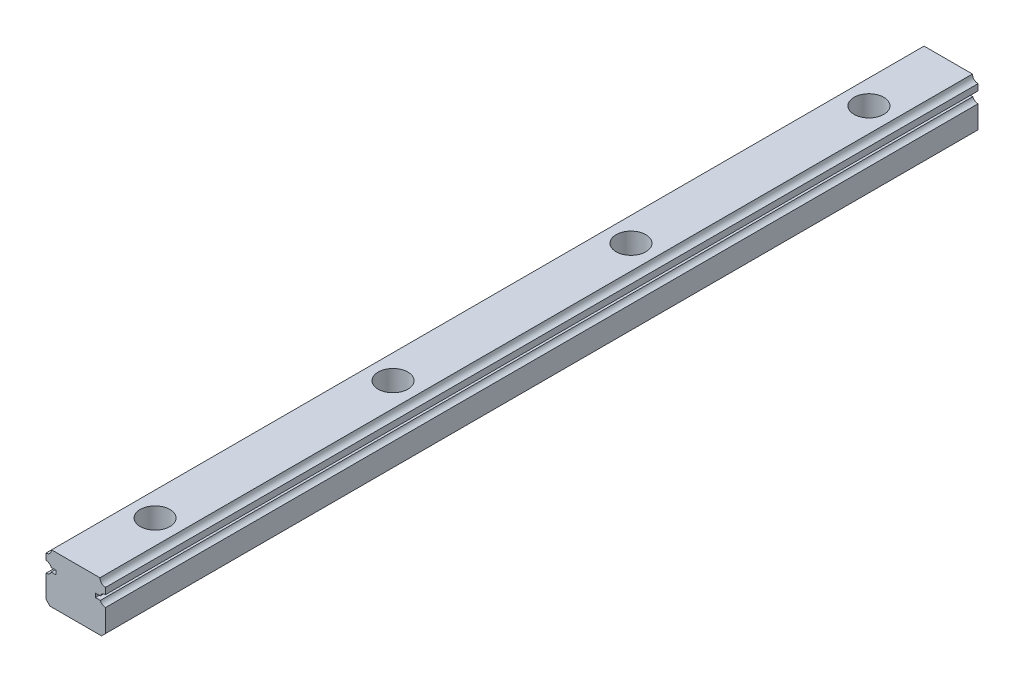
SolidWorks part; units mm, degrees
ref_plane "Front" through (0, 0, 0) normal (0, 0, 1) x (1, 0, 0)
ref_plane "Top" through (0, 0, 0) normal (0, 1, 0) x (1, 0, 0)
ref_plane "Right" through (0, 0, 0) normal (1, 0, 0) x (0, 0, -1)
sketch "15mm" plane through (0, 0, 0) normal (0, 0, 1) x (1, 0, 0)
  line L0 (0, 0) -> (0, 12.5) construction
  line L2 (4.95, 7.6) -> (6.1923, 7.6)
  line L3 (4.95, 8.6) -> (4.95, 7.6)
  line L4 (6.1923, 8.6) -> (4.95, 8.6)
  line L5 (7.5, 11.1) -> (7.5, 9.5)
  line L6 (-6.1, 12.5) -> (6.1, 12.5)
  line L7 (-7.5, 9.5) -> (-7.5, 11.1)
  line L8 (-4.95, 8.6) -> (-6.1923, 8.6)
  line L9 (-4.95, 7.6) -> (-4.95, 8.6)
  line L10 (-6.1923, 7.6) -> (-4.95, 7.6)
  line L11 (-7.5, 1) -> (-7.5, 6.7)
  line L12 (-6.5, 0) -> (-7.5, 1)
  line L13 (6.5, 0) -> (-6.5, 0)
  line L14 (7.5, 1) -> (6.5, 0)
  line L15 (7.5, 6.7) -> (7.5, 1)
  arc A0 (6.1923, 8.6) -> (7.5, 9.5) centre (7.5, 8.1) cw
  arc A1 (7.5, 11.1) -> (6.1, 12.5) centre (7.5, 12.5) cw
  arc A2 (-6.1, 12.5) -> (-7.5, 11.1) centre (-7.5, 12.5) cw
  arc A3 (-7.5, 9.5) -> (-6.1923, 8.6) centre (-7.5, 8.1) cw
  arc A4 (-6.1923, 7.6) -> (-7.5, 6.7) centre (-7.5, 8.1) cw
  arc A5 (7.5, 6.7) -> (6.1923, 7.6) centre (7.5, 8.1) cw
extrude "Extrude1" add sketch "15mm" along normal mid plane 220
sketch "Sketch1" plane through (0, 0, 0) normal (1, 0, 0) x (0, 0, -1)
  line L0 (-90, 0) -> (-90, 12.5) construction
  line L1 (-110, 0) -> (110, 0) construction
  line L2 (-110, 12.5) -> (110, 12.5) construction
  line L3 (-90, 12.5) -> (-86.25, 12.5)
  line L4 (-86.25, 12.5) -> (-86.25, 7.2)
  line L5 (-86.25, 7.2) -> (-87.75, 7.2)
  line L6 (-87.75, 7.2) -> (-87.75, 0)
  line L7 (-87.75, 0) -> (-90, 0)
  line L8 (-90, 0) -> (-90, 12.5)
  line L9 (-110, 1) -> (-110, 6.7) construction
  dimension "D1" = 4.5
  dimension "D2" = 7.5
  dimension "D3" = 5.3
  dimension "D4" = 20
revolve "Cut-Revolve1" cut sketch "Sketch1" angle 360 about L0
sketch "Sketch2" plane through (0, 0, 0) normal (1, 0, 0) x (0, 0, -1)
  line L0 (90, 12.5) -> (90, 0) construction
  line L1 (-110, 12.5) -> (110, 12.5) construction
  line L2 (-110, 0) -> (110, 0) construction
  line L3 (90, 0) -> (92.25, 0)
  line L4 (92.25, 0) -> (92.25, 7.2)
  line L5 (92.25, 7.2) -> (93.75, 7.2)
  line L6 (93.75, 7.2) -> (93.75, 12.5)
  line L7 (93.75, 12.5) -> (90, 12.5)
  line L8 (90, 0) -> (110, 0) construction
  line L9 (-87.75, 0) -> (-90, 0) construction
  line L10 (-90, 12.5) -> (-86.25, 12.5) construction
  line L11 (-110, 0) -> (-90, 0) construction
  line L12 (-86.25, 7.2) -> (-87.75, 7.2) construction
  line L13 (90, 12.5) -> (90, 0)
revolve "Cut-Revolve2" cut sketch "Sketch2" angle 360 about L0
ref_axis "Axis1" through (0, 0, -121) along (0, 0, 1)
pattern_linear "LPattern1" count 3 spacing 60 along (0, 0, 1) of "Cut-Revolve2"
